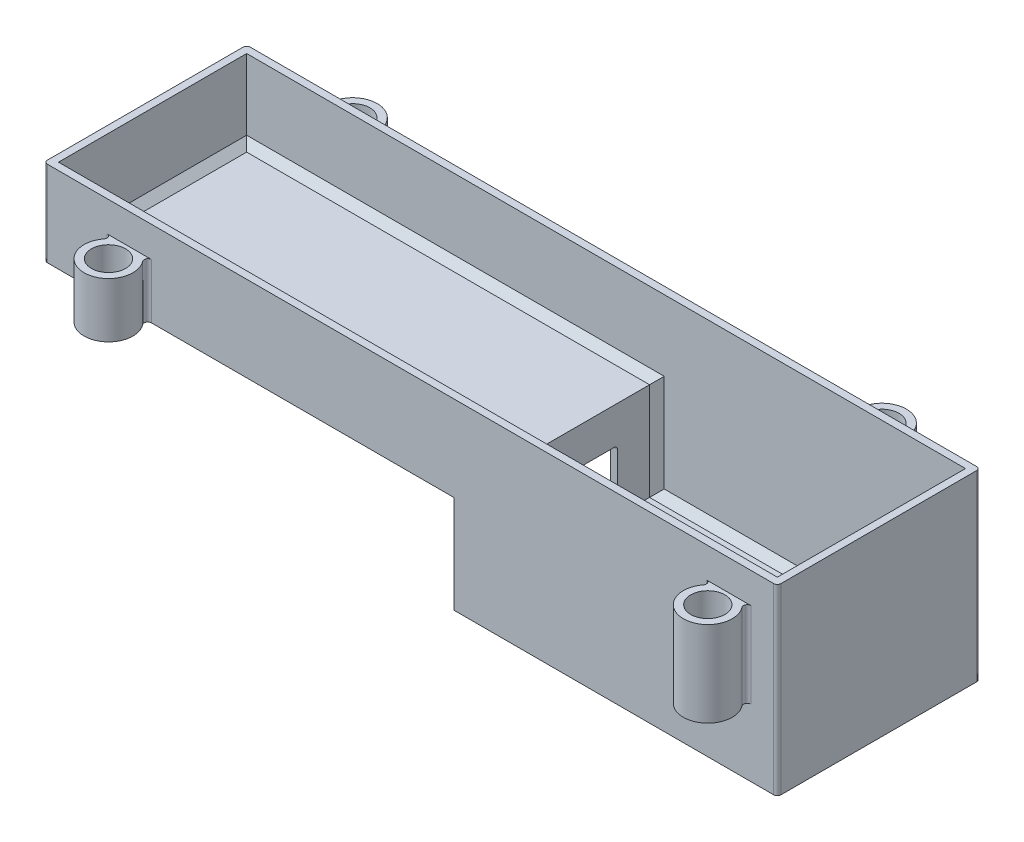
SolidWorks part; units mm, degrees
ref_plane "Front Plane" through (0, 0, 0) normal (0, 0, 1) x (1, 0, 0)
ref_plane "Bottom Plane" through (0, 0, 0) normal (0, 1, 0) x (1, 0, 0)
ref_plane "Right Plane" through (0, 0, 0) normal (1, 0, 0) x (0, 0, -1)
sketch "Sketch1" plane through (0, 0, 0) normal (0, 1, 0) x (1, 0, 0)
  line L0 (58.925, 15.425) -> (-58.925, 15.425)
  line L1 (60.125, -16.625) -> (-60.125, -16.625)
  line L2 (60.125, -16.625) -> (60.125, 16.625)
  line L3 (60.125, 16.625) -> (-60.125, 16.625)
  line L4 (-60.125, -16.625) -> (-60.125, 16.625)
  line L5 (60.125, -16.625) -> (-60.125, 16.625) construction
  line L6 (60.125, 16.625) -> (-60.125, -16.625) construction
  line L7 (-58.925, -15.425) -> (-58.925, 15.425)
  line L8 (58.925, -15.425) -> (-58.925, -15.425)
  line L9 (58.925, -15.425) -> (58.925, 15.425)
  line L10 (-1000, 0) -> (49000, 0) construction
  line L11 (7.125, -974.3115) -> (7.125, 49025.6885) construction
  circle A0 centre (-46.125, -20.025) radius 4
  circle A1 centre (52.125, -20.025) radius 4
  circle A2 centre (-46.125, 20.025) radius 4
  circle A3 centre (40.625, 20.025) radius 4
  circle A4 centre (-46.125, 20.025) radius 2.8
  circle A5 centre (-46.125, -20.025) radius 2.8
  circle A6 centre (52.125, -20.025) radius 2.8
  circle A7 centre (40.625, 20.025) radius 2.8
  circle A8 centre (-46.125, 20.025) radius 1.3
  circle A9 centre (-46.125, -20.025) radius 1.3
  circle A10 centre (52.125, -20.025) radius 1.3
  circle A11 centre (40.625, 20.025) radius 1.3
  point P0 (0, 0)
  dimension "D4" = 8
  dimension "D6" = 8.6
  dimension "D7" = 12
  dimension "D5" = 18
  dimension "D10" = 1.2
  dimension "D11" = 2.6
  dimension "D1" = 120.25
  dimension "D2" = 33.25
  dimension "D8" = 23.5
  dimension "D9" = 53
  dimension "D3" = 1.2
extrude "Boss-Extrude1" add sketch "Sketch1" along normal blind 14 contours L1 L4 L3 L2
extrude "Cut-Extrude1" cut sketch "Sketch1<3>" along normal up to next from offset 1.2 contours L0 L7 L8 L9
sketch "Sketch1<3>" plane through (0, 0, 0) normal (0, 1, 0) x (1, 0, 0) same geometry as "Sketch1"
sketch "Sketch2" plane through (0, 0, 0) normal (0, 1, 0) x (1, 0, 0)
  line L0 (60.125, -16.625) -> (-60.125, -16.625) construction
  line L1 (60.125, 16.625) -> (7.125, 16.625)
  line L2 (60.125, 16.625) -> (60.125, -16.625)
  line L3 (60.125, -16.625) -> (7.125, -16.625)
  line L4 (7.125, 16.625) -> (7.125, -16.625)
  line L5 (7.125, -200974.3115) -> (7.125, 249025.6885) construction
  line L6 (58.925, 15.425) -> (8.325, 15.425)
  line L7 (8.325, 15.425) -> (8.325, -15.425)
  line L8 (58.925, -15.425) -> (8.325, -15.425)
  line L9 (58.925, 15.425) -> (58.925, -15.425)
  dimension "D1" = 1.2
extrude "Boss-Extrude2" add sketch "Sketch2" against normal blind 16 contours L4 L3 L2 L1
extrude "Cut-Extrude2" cut sketch "Sketch2<3>" against normal offset from surface 1.2 and the other way up to next contours L7 L8 L9 L6 up to face at (33.625, -16, 0)
sketch "Sketch2<3>" plane through (0, 0, 0) normal (0, 1, 0) x (1, 0, 0) same geometry as "Sketch2"
sketch "Sketch3" plane through (0, 0, 0) normal (1, 0, 0) x (0, 0, -1)
  line L0 (0, -1000) -> (0, 49000) construction
  line L1 (-16.625, 0) -> (16.625, 0) construction
  line L10 (9, -14.8) -> (-9, -14.8)
  line L11 (9, -14.8) -> (9, -4.8)
  line L12 (9, -4.8) -> (-9, -4.8)
  line L13 (-9, -14.8) -> (-9, -4.8)
  line L14 (9, -14.8) -> (-9, -4.8) construction
  line L15 (9, -4.8) -> (-9, -14.8) construction
  line L18 (-15.425, -14.8) -> (15.425, -14.8) construction
  point P5 (0, 0)
  point P9 (0, -9.8)
  dimension "D3" = 10
  dimension "D4" = 18
extrude "Cut-Extrude4" cut sketch "Sketch3" along normal up to surface (8.325 mm away) up to face at (8.325, -6.8, 0)
extrude "Boss-Extrude3" add sketch "Sketch1<4>" along normal offset from surface (9 mm away) 5 contours A1 | A0 | A3 | A2 up to face at (0, 14, 0)
sketch "Sketch1<4>" plane through (0, 0, 0) normal (0, 1, 0) x (1, 0, 0) same geometry as "Sketch1"
extrude "Boss-Extrude4" add sketch "Sketch1<5>" against normal blind 5 contours A1
sketch "Sketch1<5>" plane through (0, 0, 0) normal (0, 1, 0) x (1, 0, 0) same geometry as "Sketch1"
extrude "Cut-Extrude5" cut sketch "Sketch1<6>" against normal blind 6 from surface contours A6 | A7 | A4 | A5 starting at face at (-46.125, 9, -20.325)
sketch "Sketch1<6>" plane through (0, 0, 0) normal (0, 1, 0) x (1, 0, 0) same geometry as "Sketch1"
extrude "Cut-Extrude6" cut sketch "Sketch1<7>" along normal blind 7 from surface contours A6 starting at face at (52.125, -5, 20.325)
sketch "Sketch1<7>" plane through (0, 0, 0) normal (0, 1, 0) x (1, 0, 0) same geometry as "Sketch1"
extrude "Cut-Extrude7" cut sketch "Sketch1<8>" along normal through all both and the other way through all contours A8 | A9 | A10 | A11
sketch "Sketch1<8>" plane through (0, 0, 0) normal (0, 1, 0) x (1, 0, 0) same geometry as "Sketch1"
extrude "Cut-Extrude8" cut sketch "Sketch1<9>" along normal blind 2 contours A7 | A4 | A5
sketch "Sketch1<9>" plane through (0, 0, 0) normal (0, 1, 0) x (1, 0, 0) same geometry as "Sketch1"
fillet "Fillet1" radius 0.6 16 edges at (50.0179, 2, 16.625) (54.2321, 2, 16.625) (38.5179, 4.5, -16.625) (42.7321, 4.5, -16.625) (-44.0179, 4.5, -16.625) (-48.2321, 4.5, -16.625) (-48.2321, 4.5, 16.625) (-44.0179, 4.5, 16.625) (60.125, -1, 16.625) (60.125, -1, -16.625) (-60.125, 7, -16.625) (-60.125, 7, 16.625) (7.725, -14.8, -9) (7.725, -14.8, 9) (7.725, -4.8, 9) (7.725, -4.8, -9)
chamfer "Chamfer1" distance 1.2 angle 45 8 edges at (-25.3, 1.2, -15.425) (-58.925, 1.2, 0) (-25.3, 1.2, 15.425) (33.625, -14.8, 15.425) (33.625, -14.8, -15.425) (8.325, -6.8, -15.425) (8.325, -6.8, 15.425) (58.925, -14.8, 0)
